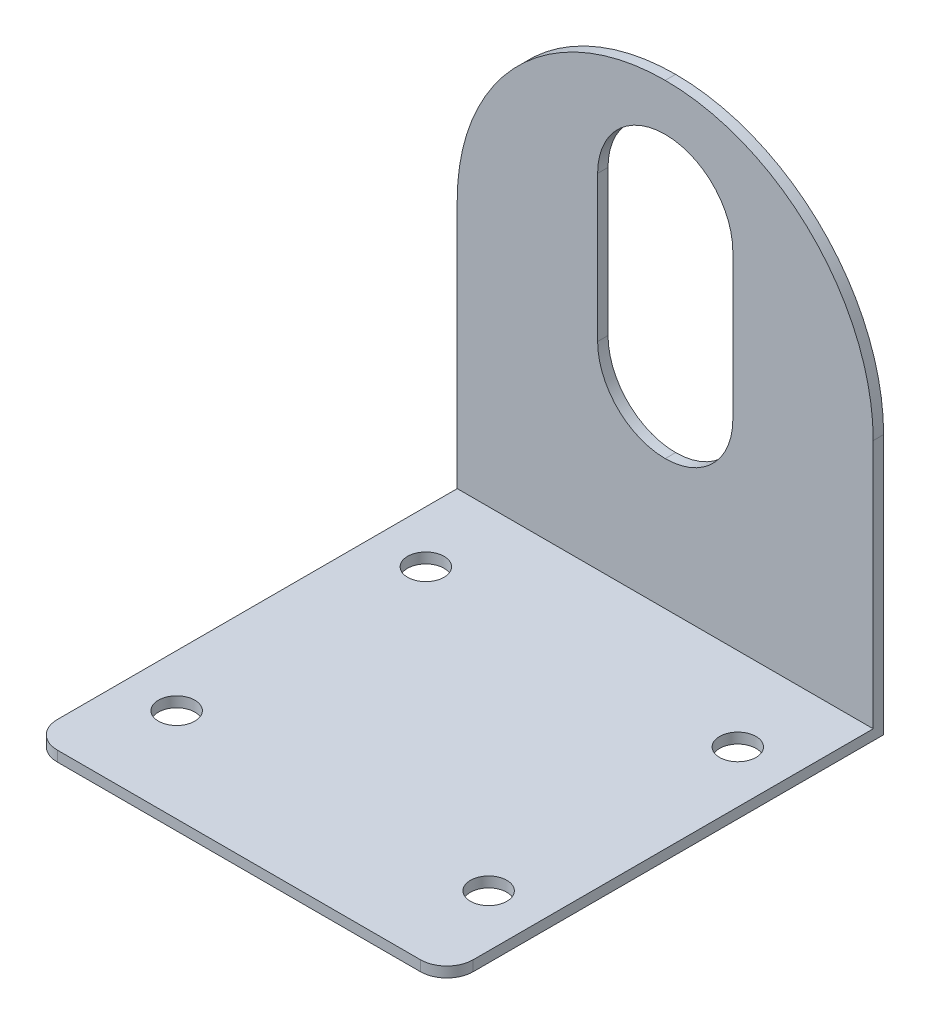
SolidWorks part; units mm, degrees
ref_plane "Front Plane" through (0, 0, 0) normal (0, 0, 1) x (1, 0, 0)
ref_plane "Top Plane" through (0, 0, 0) normal (0, 1, 0) x (1, 0, 0)
ref_plane "Right Plane" through (0, 0, 0) normal (1, 0, 0) x (0, 0, -1)
sketch "Sketch1" plane through (0, 0, 0) normal (0, 0, 1) x (1, 0, 0)
  line L1 (0, 0) -> (40, 0)
  line L2 (0, 0) -> (0, 45)
  line L3 (0, 45) -> (40, 45)
  line L4 (40, 0) -> (40, 45)
  dimension "D1" = 40
  dimension "D2" = 45
extrude "Vertical-Base" add sketch "Sketch1" along normal blind 1
fillet "Top-Rounding" radius 20 1 edges at (0, 45, 0.5) type face fillet first side face at (0, 22.5, 0.5) second side face at (20, 45, 0.5)
fillet "Top-Rounding-2" radius 20 1 edges at (40, 45, 0.5) type face fillet first side face at (30, 45, 0.5) second side face at (40, 22.5, 0.5)
sketch "Sketch2" plane through (0, 0, 1) normal (0, 0, 1) x (1, 0, 0)
  line L0 (40, 0) -> (40, 25) construction
  line L1 (0, 0) -> (40, 0)
  line L2 (0, 0) -> (0, 1)
  line L3 (0, 1) -> (40, 1)
  line L4 (40, 0) -> (40, 1)
  dimension "D1" = 1
extrude "Horizontal-Base" add sketch "Sketch2" along normal blind 41
fillet "Fillet3" radius 2.54 1 edges at (40, 0.5, 42) type face fillet first side face at (40, 8.6667, 14.3333) second side face at (20, 0.5, 42)
fillet "Fillet4" radius 2.54 1 edges at (0, 0.5, 42) type face fillet first side face at (0, 8.6667, 14.3333) second side face at (18.73, 0.5, 42)
sketch "Sketch3" plane through (0, 1, 0) normal (0, 1, 0) x (1, 0, 0)
  line L0 (20, -42) -> (20, 0) construction
  line L1 (37.46, -42) -> (2.54, -42) construction
  line L2 (20, -21) -> (40, -21) construction
  line L3 (40, -39.46) -> (40, -1) construction
  line L4 (20, -21) -> (0, -21) construction
  line L5 (0, -39.46) -> (0, -1) construction
  line L6 (20, -42) -> (35, -42) construction
  line L7 (20, -42) -> (5, -42) construction
  line L8 (35, -21) -> (35, -32.9797) construction
  line L9 (35, -21) -> (35, -9.0203) construction
  line L10 (5, -21) -> (5, -32.9797) construction
  line L11 (5, -9.0203) -> (5, -21) construction
  circle A0 centre (35, -32.9797) radius 1.75
  circle A1 centre (5, -32.9797) radius 1.75
  circle A2 centre (5, -9.0203) radius 1.75
  circle A3 centre (35, -9.0203) radius 1.75
  dimension "D1" = 15
extrude "Mounting Holes" cut sketch "Sketch3" against normal through all
sketch "Sketch5" plane through (0, 0, 0) normal (0, 0, -1) x (-1, 0, 0)
  line L0 (-20, 0) -> (-20, 27) construction
  line L1 (0, 0) -> (-40, 0) construction
  line L3 (-26.5, 13.5) -> (-13.5, 13.5)
  line L4 (-26.5, 13.5) -> (-26.5, 40.5)
  line L5 (-26.5, 40.5) -> (-13.5, 40.5)
  line L6 (-13.5, 13.5) -> (-13.5, 40.5)
  line L7 (-26.5, 13.5) -> (-13.5, 40.5) construction
  line L8 (-26.5, 40.5) -> (-13.5, 13.5) construction
extrude "Cut-Extrude2" cut sketch "Sketch5" against normal through all
fillet "Fillet5" radius 6.5 1 edges at (13.5, 40.5, 0.5) type face fillet first side face at (20, 40.5, 0.5) second side face at (13.5, 27, 0.5)
fillet "Fillet6" radius 6.5 1 edges at (26.5, 40.5, 0.5) type face fillet first side face at (23.25, 40.5, 0.5) second side face at (26.5, 27, 0.5)
fillet "Fillet7" radius 6.5 1 edges at (13.5, 13.5, 0.5) type face fillet first side face at (13.5, 23.75, 0.5) second side face at (20, 13.5, 0.5)
fillet "Fillet8" radius 6.5 1 edges at (26.5, 13.5, 0.5) type face fillet first side face at (23.25, 13.5, 0.5) second side face at (26.5, 23.75, 0.5)
